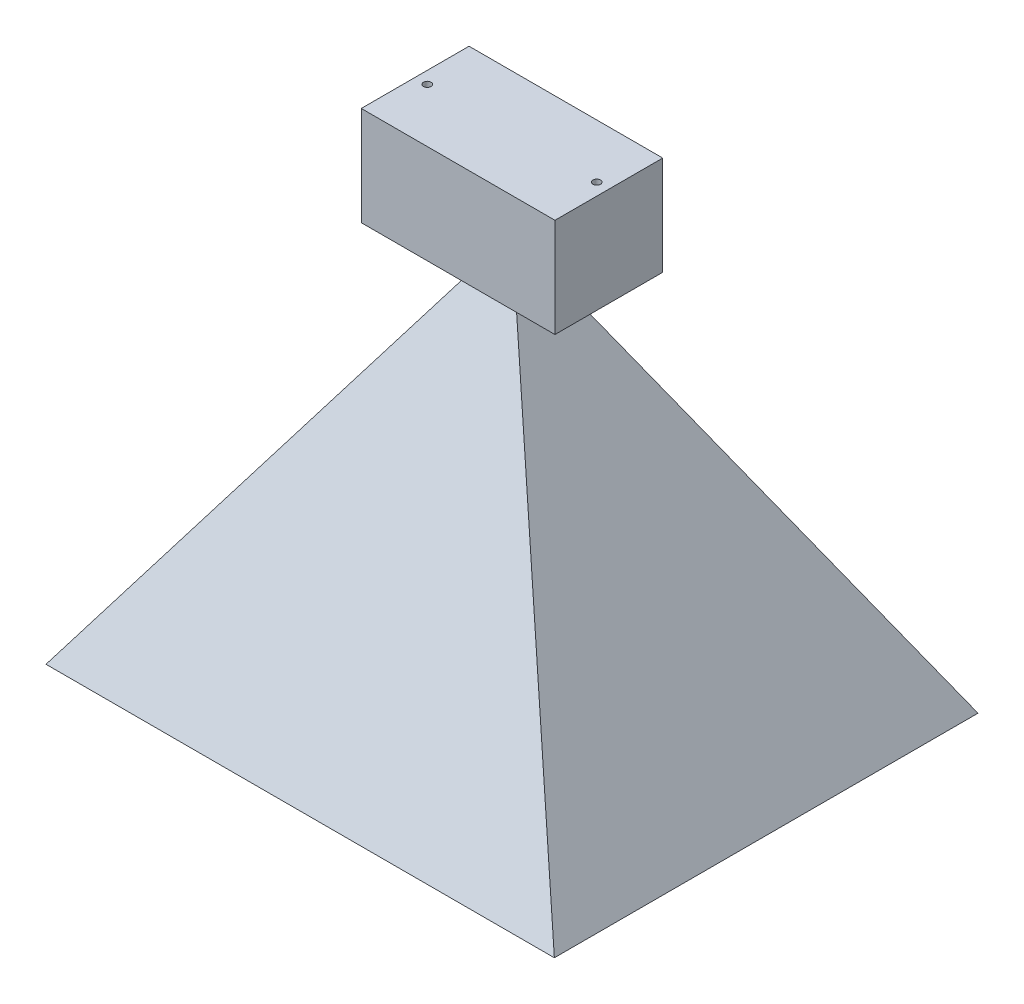
SolidWorks part; units mm, degrees
ref_plane "Front Plane" through (0, 0, 0) normal (0, 0, 1) x (1, 0, 0)
ref_plane "Top Plane" through (0, 0, 0) normal (0, 1, 0) x (1, 0, 0)
ref_plane "Right Plane" through (0, 0, 0) normal (1, 0, 0) x (0, 0, -1)
ref_plane "distance of measurement" through (0, 114.3, 0) normal (0, 1, 0) x (1, 0, 0)
sketch "Sketch1" plane through (0, 0, 0) normal (0, 1, 0) x (1, 0, 0)
  line L1 (-76.2, -63.5) -> (76.2, -63.5)
  line L2 (-76.2, -63.5) -> (-76.2, 63.5)
  line L3 (-76.2, 63.5) -> (76.2, 63.5)
  line L4 (76.2, -63.5) -> (76.2, 63.5)
  line L5 (-76.2, -63.5) -> (76.2, 63.5) construction
  line L6 (-76.2, 63.5) -> (76.2, -63.5) construction
  point P0 (0, 0)
  dimension "D1" = 152.4
  dimension "D2" = 127
sketch "Sketch2" plane through (0, 114.3, 0) normal (0, 1, 0) x (1, 0, 0)
  line L0 (-76.2, -63.5) -> (76.2, 63.5) construction
  line L1 (-2.4731, -2.0609) -> (2.4731, -2.0609)
  line L2 (-2.4731, -2.0609) -> (-2.4731, 2.0609)
  line L3 (-2.4731, 2.0609) -> (2.4731, 2.0609)
  line L4 (2.4731, -2.0609) -> (2.4731, 2.0609)
  line L5 (-2.4731, -2.0609) -> (2.4731, 2.0609) construction
  line L6 (-2.4731, 2.0609) -> (2.4731, -2.0609) construction
  point P0 (0, 0)
loft "FOV" add profiles "Sketch2", "Sketch1" connector at (-2.4731, 114.3, 2.0609) connector at (-76.2, 0, 63.5)
sketch "Sketch3" plane through (0, 114.3, 0) normal (0, 1, 0) x (1, 0, 0)
  circle A0 centre (0, 0) radius 8.509
  dimension "D1" = 17.018
extrude "camera lens" add sketch "Sketch3" along normal blind 0.254
sketch "Sketch4" plane through (0, 114.554, 0) normal (0, 1, 0) x (1, 0, 0)
  line L1 (29.0322, -16.1544) -> (-29.0322, -16.1544)
  line L2 (29.0322, -16.1544) -> (29.0322, 16.1544)
  line L3 (29.0322, 16.1544) -> (-29.0322, 16.1544)
  line L4 (-29.0322, -16.1544) -> (-29.0322, 16.1544)
  line L5 (29.0322, -16.1544) -> (-29.0322, 16.1544) construction
  line L6 (29.0322, 16.1544) -> (-29.0322, -16.1544) construction
  point P0 (0, 0)
  dimension "D1" = 58.0644
  dimension "D2" = 32.3088
extrude "camera holder" add sketch "Sketch4" along normal blind 29.6672
ref_point "centre of vision"
ref_point "direction reference"
sketch "reference points sketch" plane through (0, 0, 0) normal (0, -1, 0) x (1, 0, 0)
  line L0 (-76.2, 63.5) -> (76.2, 63.5) construction
  line L1 (76.2, 63.5) -> (76.2, -63.5) construction
  line L2 (76.2, -63.5) -> (-76.2, -63.5) construction
  line L3 (-76.2, -63.5) -> (-76.2, 63.5) construction
  line L4 (-76.2, 63.5) -> (76.2, -63.5) construction
  line L5 (-76.2, -63.5) -> (76.2, 63.5) construction
  point P0 (0, 63.5)
  point P1 (76.2, 0)
  point P4 (0, -63.5)
  point P7 (-76.2, 0)
  point P10 (-38.1, 0)
  point P13 (38.1, 0)
  point P14 (0, 31.75)
  point P15 (0, -31.75)
  point P16 (38.1, -31.75)
  point P17 (38.1, 31.75)
  point P20 (-38.1, 31.75)
  point P23 (-38.1, -31.75)
  point P24 (-76.2, 63.5)
  point P26 (76.2, 63.5)
  point P28 (76.2, -63.5)
  point P30 (-76.2, -63.5)
  dimension "D1" = 31.75
  dimension "D2" = 0
  dimension "D3" = 38.1
  dimension "D4" = 31.75
  dimension "D5" = 31.75
  dimension "D6" = 38.1
  dimension "D7" = 38.1
  dimension "D8" = 31.75
  dimension "D9" = 38.1
  dimension "D10" = 31.75
  dimension "D11" = 38.1
  dimension "D12" = 38.1
ref_point "direction reference 0"
ref_point "direction reference 1"
ref_point "direction reference 2"
ref_point "direction reference 3"
ref_point "direction reference 4"
ref_point "direction reference 5"
ref_point "direction reference 6"
ref_point "direction reference 7"
ref_point "direction reference 8"
ref_point "direction reference 9"
ref_point "direction reference 10"
ref_point "direction reference 11"
ref_point "direction reference 12"
ref_point "direction reference 13"
ref_point "direction reference 14"
ref_point "direction reference 15"
hole_wizard "#4-40 Tapped Hole1" positions "Sketch6" profile "Sketch5" tap size "#4-40" standard "ANSI Inch" end condition up to next
sketch "Sketch6" plane through (0, 144.2212, 0) normal (0, 1, 0) x (1, 0, 0)
  point P0 (-25.4, 0)
  point P2 (25.4, 0)
  dimension "D1" = 25.4
  dimension "D2" = 25.4
sketch "Sketch5" plane through (-25.4, 144.2212, 0) normal (1, 0, 0) x (0, 0, 1)
  line L0 (0, 0) -> (0, 29.6672)
  line L1 (0, 29.6672) -> (1.1303, 29.6672)
  line L2 (1.1303, 29.6672) -> (1.1303, 0)
  line L5 (1.1303, 0) -> (0, 0)
  line L11 (0, -6.35) -> (0, 107.95) construction
  dimension "Thru Tap Drill Dia." = 2.2606
  dimension "Thru Tap Drill Depth" = 29.6672
cosmetic thread "Hole Thread1" parameters "D2"=2.8448
cosmetic thread "Hole Thread2" parameters "D2"=2.8448
